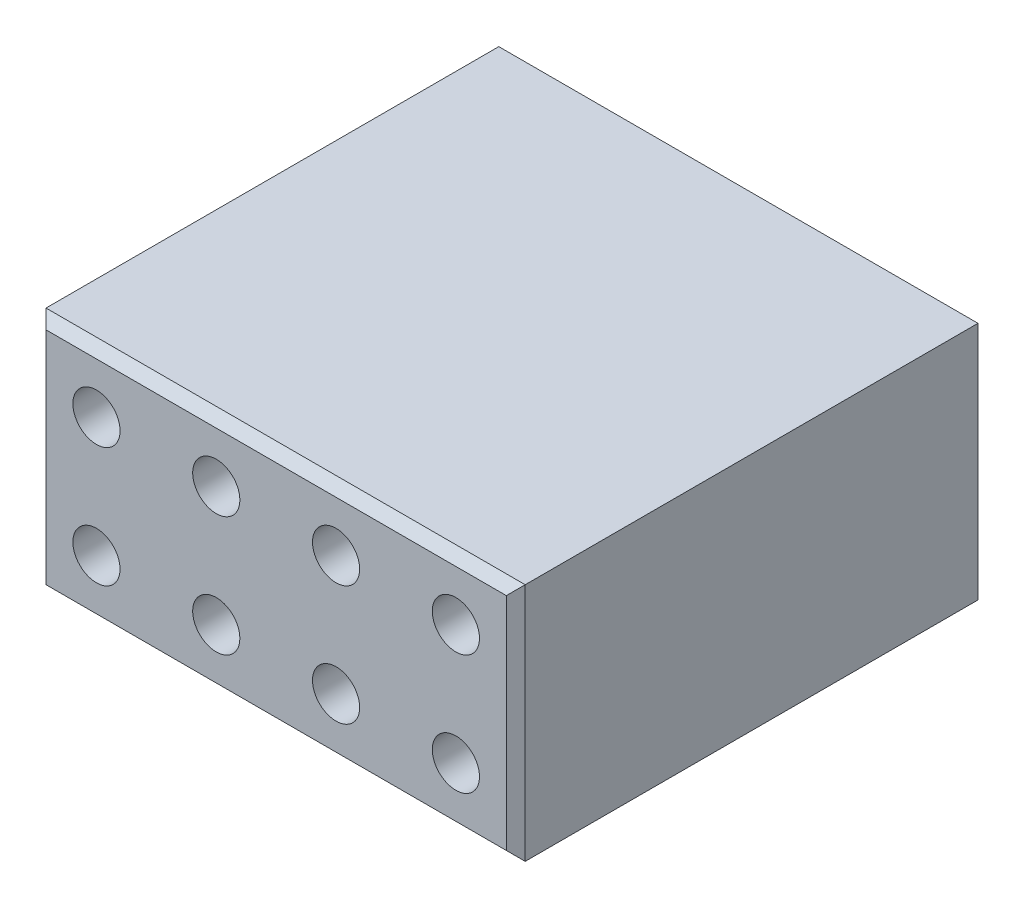
SolidWorks part; units mm, degrees
ref_plane "Front Plane" through (0, 0, 0) normal (0, 0, 1) x (1, 0, 0)
ref_plane "Top Plane" through (0, 0, 0) normal (0, 1, 0) x (1, 0, 0)
ref_plane "Right Plane" through (0, 0, 0) normal (1, 0, 0) x (0, 0, -1)
sketch "Sketch1" plane through (0, 0, 0) normal (0, 0, 1) x (1, 0, 0)
  line L0 (0, 2.54) -> (0, 0) construction
  line L1 (-5.08, 2.54) -> (5.08, 2.54)
  line L2 (-5.08, 2.54) -> (-5.08, -2.54)
  line L3 (-5.08, -2.54) -> (5.08, -2.54)
  line L4 (5.08, 2.54) -> (5.08, -2.54)
  line L5 (0, 0) -> (0, -2.54) construction
  line L6 (-1.77, 1.77) -> (-0.77, 1.77)
  line L7 (-4.31, 1.77) -> (-3.31, 1.77)
  line L8 (-4.31, 1.77) -> (-4.31, 0.77)
  line L9 (-4.31, 0.77) -> (-3.31, 0.77)
  line L10 (-3.31, 1.77) -> (-3.31, 0.77)
  line L11 (-1.77, 1.77) -> (-1.77, 0.77)
  line L12 (-1.77, 0.77) -> (-0.77, 0.77)
  line L13 (-0.77, 1.77) -> (-0.77, 0.77)
  line L14 (0.77, 1.77) -> (1.77, 1.77)
  line L15 (0.77, 1.77) -> (0.77, 0.77)
  line L16 (0.77, 0.77) -> (1.77, 0.77)
  line L17 (1.77, 1.77) -> (1.77, 0.77)
  line L18 (3.31, 1.77) -> (4.31, 1.77)
  line L19 (3.31, 1.77) -> (3.31, 0.77)
  line L20 (3.31, 0.77) -> (4.31, 0.77)
  line L21 (4.31, 1.77) -> (4.31, 0.77)
  line L22 (-1.77, -0.77) -> (-0.77, -0.77)
  line L23 (-1.77, -0.77) -> (-1.77, -1.77)
  line L24 (-1.77, -1.77) -> (-0.77, -1.77)
  line L25 (-0.77, -0.77) -> (-0.77, -1.77)
  line L26 (0.77, -0.77) -> (1.77, -0.77)
  line L27 (0.77, -0.77) -> (0.77, -1.77)
  line L28 (0.77, -1.77) -> (1.77, -1.77)
  line L29 (1.77, -0.77) -> (1.77, -1.77)
  line L30 (3.31, -0.77) -> (4.31, -0.77)
  line L31 (3.31, -0.77) -> (3.31, -1.77)
  line L32 (3.31, -1.77) -> (4.31, -1.77)
  line L33 (4.31, -0.77) -> (4.31, -1.77)
  line L34 (-4.31, -0.77) -> (-3.31, -0.77)
  line L35 (-4.31, -0.77) -> (-4.31, -1.77)
  line L36 (-4.31, -1.77) -> (-3.31, -1.77)
  line L37 (-3.31, -0.77) -> (-3.31, -1.77)
  line L38 (-0.77, 0.77) -> (-0.77, -0.77) construction
  line L39 (0.77, 0.77) -> (0.77, -0.77) construction
  line L40 (-0.77, 0) -> (0.77, 0) construction
  line L41 (-3.81, 1.77) -> (-3.81, 0.77) construction
  line L42 (-4.31, 1.27) -> (-3.31, 1.27) construction
  line L43 (-3.81, 1.27) -> (-3.81, 2.54) construction
  line L44 (-3.81, 1.27) -> (-5.08, 1.27) construction
  line L45 (-1.27, 1.77) -> (-1.27, 0.77) construction
  line L46 (-3.81, 1.27) -> (-2.54, 1.27) construction
  line L47 (-1.77, 1.27) -> (-0.77, 1.27) construction
  line L48 (-2.54, 1.27) -> (-1.27, 1.27) construction
  dimension "D3" = 2.54
  dimension "D4" = 2.54
  dimension "D5" = 1
  dimension "D1" = 4
  dimension "D2" = 2
extrude "Boss-Extrude2" add sketch "Sketch1" along normal blind 8
sketch "Sketch2" plane through (0, 0, 8) normal (0, 0, 1) x (1, 0, 0)
  line L0 (-3.81, -0.77) -> (-3.81, -1.77) construction
  line L1 (-5.08, 2.54) -> (5.08, 2.54)
  line L2 (-5.08, 2.54) -> (-5.08, -2.54)
  line L3 (-5.08, -2.54) -> (5.08, -2.54)
  line L4 (5.08, 2.54) -> (5.08, -2.54)
  line L5 (-4.31, -0.77) -> (-3.31, -0.77) construction
  line L6 (-4.31, -1.77) -> (-3.31, -1.77) construction
  line L8 (-4.31, -0.77) -> (-4.31, -1.77) construction
  line L9 (-4.31, -1.27) -> (-3.31, -1.27) construction
  line L10 (-3.31, -0.77) -> (-3.31, -1.77) construction
  circle A0 centre (-3.81, 1.27) radius 0.5
  circle A1 centre (-1.27, 1.27) radius 0.5
  circle A2 centre (1.27, 1.27) radius 0.5
  circle A3 centre (3.81, 1.27) radius 0.5
  circle A4 centre (-1.27, -1.27) radius 0.5
  circle A5 centre (1.27, -1.27) radius 0.5
  circle A6 centre (3.81, -1.27) radius 0.5
  circle A7 centre (-3.81, -1.27) radius 0.5
  dimension "D1" = 1
  dimension "D2" = 4
  dimension "D3" = 2
extrude "Boss-Extrude3" add sketch "Sketch2" along normal blind 2
chamfer "Chamfer1" distance 0.2 angle 45 36 edges at (-3.81, -0.77, 0) (-3.31, -1.27, 0) (-3.81, -1.77, 0) (-4.31, -1.27, 0) (1.27, -0.77, 0) (1.77, -1.27, 0) (1.27, -1.77, 0) (0.77, -1.27, 0) (3.81, 1.77, 0) (4.31, 1.27, 0) (3.81, 0.77, 0) (3.31, 1.27, 0) (-1.27, 1.77, 0) (-0.77, 1.27, 0) (-1.27, 0.77, 0) (-1.77, 1.27, 0) (0, -2.54, 0) (5.08, 0, 0) (0, 2.54, 0) (-5.08, 0, 0) (-3.81, 1.77, 0) (-3.31, 1.27, 0) (-3.81, 0.77, 0) (-4.31, 1.27, 0) (1.27, 1.77, 0) (1.77, 1.27, 0) (1.27, 0.77, 0) (0.77, 1.27, 0) (-1.27, -0.77, 0) (-0.77, -1.27, 0) (-1.27, -1.77, 0) (-1.77, -1.27, 0) (3.81, -0.77, 0) (4.31, -1.27, 0) (3.81, -1.77, 0) (3.31, -1.27, 0)
chamfer "Chamfer2" distance 0.2 angle 45 4 edges at (5.08, 0, 10) (0, -2.54, 10) (-5.08, 0, 10) (0, 2.54, 10)
other "CPoint4"
ref_axis "Axis4" through (-3.81, 1.27, 0) along (0, 0, 1)
other "CPoint5"
ref_axis "Axis5" through (-3.81, -1.27, 0) along (0, 0, 1)
other "CPoint6"
ref_axis "Axis6" through (-1.27, 1.27, 0) along (0, 0, 1)
other "CPoint7"
ref_axis "Axis7" through (-1.27, -1.27, 0) along (0, 0, 1)
other "CPoint8"
ref_axis "Axis8" through (1.27, 1.27, 0) along (0, 0, 1)
other "CPoint9"
ref_axis "Axis9" through (1.27, -1.27, 0) along (0, 0, 1)
other "CPoint10"
ref_axis "Axis10" through (3.81, 1.27, 0) along (0, 0, 1)
other "CPoint11"
ref_axis "Axis11" through (3.81, -1.27, 0) along (0, 0, 1)
